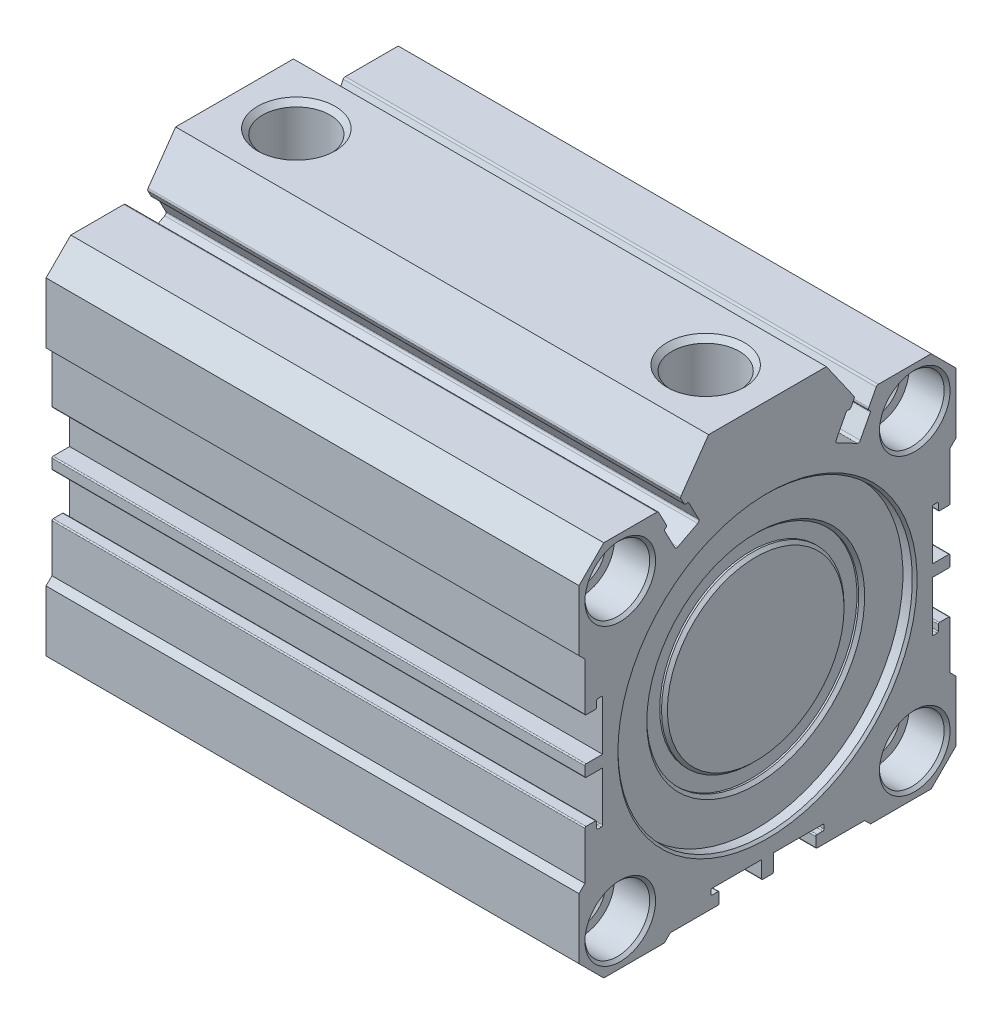
SolidWorks part; units mm, degrees
ref_plane "前视基准面" through (0, 0, 0) normal (0, 0, 1) x (1, 0, 0)
ref_plane "上视基准面" through (0, 0, 0) normal (0, 1, 0) x (1, 0, 0)
ref_plane "右视基准面" through (0, 0, 0) normal (1, 0, 0) x (0, 0, -1)
sketch "草图1" plane through (0, 0, 0) normal (1, 0, 0) x (0, 0, -1)
  line L0 (-32, -17.5) -> (-32, -27.8)
  line L1 (-32, -27.8) -> (-27.8, -32)
  line L2 (-27.8, -32) -> (-17.5, -32)
  line L3 (-17.5, -32) -> (-16.5, -31)
  line L4 (-16.5, -31) -> (-8.4, -31)
  line L5 (-8.2, -30.8) -> (-8.2, -29.2)
  line L6 (-8.4, -29) -> (-9.4, -29)
  line L7 (-9.6, -28.8) -> (-9.6, -28.2)
  line L8 (-9.4, -28) -> (-1, -28)
  line L9 (-1, -28) -> (-1, -30.8)
  line L10 (-0.8, -31) -> (0.8, -31)
  line L11 (1, -30.8) -> (1, -28)
  line L12 (1, -28) -> (9.4, -28)
  line L13 (9.6, -28.2) -> (9.6, -28.8)
  line L14 (9.4, -29) -> (8.4, -29)
  line L15 (8.2, -29.2) -> (8.2, -30.8)
  line L16 (8.4, -31) -> (16.5, -31)
  line L17 (16.5, -31) -> (17.5, -32)
  line L18 (17.5, -32) -> (27.8, -32)
  line L19 (27.8, -32) -> (32, -27.8)
  line L20 (32, -27.8) -> (32, -17.5)
  line L21 (32, -17.5) -> (31, -16.5)
  line L22 (31, -16.5) -> (31, -8.4)
  line L23 (30.8, -8.2) -> (29.2, -8.2)
  line L24 (29, -8.4) -> (29, -9.4)
  line L25 (28.8, -9.6) -> (28.2, -9.6)
  line L26 (28, -9.4) -> (28, -1)
  line L27 (28, -1) -> (30.8, -1)
  line L28 (31, -0.8) -> (31, 0.8)
  line L29 (30.8, 1) -> (28, 1)
  line L30 (28, 1) -> (28, 9.4)
  line L31 (28.2, 9.6) -> (28.8, 9.6)
  line L32 (29, 9.4) -> (29, 8.4)
  line L33 (29.2, 8.2) -> (30.8, 8.2)
  line L34 (31, 8.4) -> (31, 16.5)
  line L35 (31, 16.5) -> (32, 17.5)
  line L36 (32, 17.5) -> (32, 27.8)
  line L37 (32, 27.8) -> (27.8, 32)
  line L38 (27.8, 32) -> (18.8174, 32)
  line L39 (18.4626, 31.7847) -> (17.2074, 29.3734)
  line L40 (17.4625, 28.5641) -> (15.7541, 25.2822)
  line L41 (15.2146, 25.1121) -> (11.8439, 26.8667)
  line L42 (11.6738, 27.4062) -> (13.3823, 30.6882)
  line L43 (14.1915, 30.9433) -> (14.6977, 31.9156)
  line L44 (14.6705, 32.3298) -> (10, 39)
  line L45 (10, 39) -> (-10, 39)
  line L46 (-10, 39) -> (-14.6705, 32.3298)
  line L47 (-14.6977, 31.9156) -> (-14.1915, 30.9433)
  line L48 (-13.3823, 30.6882) -> (-11.6738, 27.4062)
  line L49 (-11.8439, 26.8667) -> (-15.2146, 25.1121)
  line L50 (-15.7541, 25.2822) -> (-17.4625, 28.5641)
  line L51 (-17.2074, 29.3734) -> (-18.4626, 31.7847)
  line L52 (-18.8174, 32) -> (-27.8, 32)
  line L53 (-27.8, 32) -> (-32, 27.8)
  line L54 (-32, 27.8) -> (-32, 17.5)
  line L55 (-32, 17.5) -> (-31, 16.5)
  line L56 (-31, 16.5) -> (-31, 8.4)
  line L57 (-30.8, 8.2) -> (-29.2, 8.2)
  line L58 (-29, 8.4) -> (-29, 9.4)
  line L59 (-28.8, 9.6) -> (-28.2, 9.6)
  line L60 (-28, 9.4) -> (-28, 1)
  line L61 (-28, 1) -> (-30.8, 1)
  line L62 (-31, 0.8) -> (-31, -0.8)
  line L63 (-30.8, -1) -> (-28, -1)
  line L64 (-28, -1) -> (-28, -9.4)
  line L65 (-28.2, -9.6) -> (-28.8, -9.6)
  line L66 (-29, -9.4) -> (-29, -8.4)
  line L67 (-29.2, -8.2) -> (-30.8, -8.2)
  line L68 (-31, -8.4) -> (-31, -16.5)
  line L69 (-31, -16.5) -> (-32, -17.5)
  arc A0 (-8.4, -31) -> (-8.2, -30.8) centre (-8.4, -30.8) ccw
  arc A1 (-8.2, -29.2) -> (-8.4, -29) centre (-8.4, -29.2) ccw
  arc A2 (-9.4, -29) -> (-9.6, -28.8) centre (-9.4, -28.8) cw
  arc A3 (-9.6, -28.2) -> (-9.4, -28) centre (-9.4, -28.2) cw
  arc A4 (-1, -30.8) -> (-0.8, -31) centre (-0.8, -30.8) ccw
  arc A5 (0.8, -31) -> (1, -30.8) centre (0.8, -30.8) ccw
  arc A6 (9.4, -28) -> (9.6, -28.2) centre (9.4, -28.2) cw
  arc A7 (9.6, -28.8) -> (9.4, -29) centre (9.4, -28.8) cw
  arc A8 (8.4, -29) -> (8.2, -29.2) centre (8.4, -29.2) ccw
  arc A9 (8.2, -30.8) -> (8.4, -31) centre (8.4, -30.8) ccw
  arc A10 (31, -8.4) -> (30.8, -8.2) centre (30.8, -8.4) ccw
  arc A11 (29.2, -8.2) -> (29, -8.4) centre (29.2, -8.4) ccw
  arc A12 (29, -9.4) -> (28.8, -9.6) centre (28.8, -9.4) cw
  arc A13 (28.2, -9.6) -> (28, -9.4) centre (28.2, -9.4) cw
  arc A14 (30.8, -1) -> (31, -0.8) centre (30.8, -0.8) ccw
  arc A15 (31, 0.8) -> (30.8, 1) centre (30.8, 0.8) ccw
  arc A16 (28, 9.4) -> (28.2, 9.6) centre (28.2, 9.4) cw
  arc A17 (28.8, 9.6) -> (29, 9.4) centre (28.8, 9.4) cw
  arc A18 (29, 8.4) -> (29.2, 8.2) centre (29.2, 8.4) ccw
  arc A19 (30.8, 8.2) -> (31, 8.4) centre (30.8, 8.4) ccw
  arc A20 (18.8174, 32) -> (18.4626, 31.7847) centre (18.8174, 31.6) ccw
  arc A21 (17.2074, 29.3734) -> (17.3775, 28.8339) centre (17.5622, 29.1887) ccw
  arc A22 (17.3775, 28.8339) -> (17.4625, 28.5641) centre (17.2851, 28.6565) cw
  arc A23 (15.7541, 25.2822) -> (15.2146, 25.1121) centre (15.3993, 25.4669) cw
  arc A24 (11.8439, 26.8667) -> (11.6738, 27.4062) centre (12.0286, 27.2215) cw
  arc A25 (13.3823, 30.6882) -> (13.652, 30.7732) centre (13.5597, 30.5958) cw
  arc A26 (13.652, 30.7732) -> (14.1915, 30.9433) centre (13.8367, 31.128) ccw
  arc A27 (14.6977, 31.9156) -> (14.6705, 32.3298) centre (14.3429, 32.1003) ccw
  arc A28 (-14.6705, 32.3298) -> (-14.6977, 31.9156) centre (-14.3429, 32.1003) ccw
  arc A29 (-14.1915, 30.9433) -> (-13.652, 30.7732) centre (-13.8367, 31.128) ccw
  arc A30 (-13.652, 30.7732) -> (-13.3823, 30.6882) centre (-13.5597, 30.5958) cw
  arc A31 (-11.6738, 27.4062) -> (-11.8439, 26.8667) centre (-12.0286, 27.2215) cw
  arc A32 (-15.2146, 25.1121) -> (-15.7541, 25.2822) centre (-15.3993, 25.4669) cw
  arc A33 (-17.4625, 28.5641) -> (-17.3775, 28.8339) centre (-17.2851, 28.6565) cw
  arc A34 (-17.3775, 28.8339) -> (-17.2074, 29.3734) centre (-17.5622, 29.1887) ccw
  arc A35 (-18.4626, 31.7847) -> (-18.8174, 32) centre (-18.8174, 31.6) ccw
  arc A36 (-31, 8.4) -> (-30.8, 8.2) centre (-30.8, 8.4) ccw
  arc A37 (-29.2, 8.2) -> (-29, 8.4) centre (-29.2, 8.4) ccw
  arc A38 (-29, 9.4) -> (-28.8, 9.6) centre (-28.8, 9.4) cw
  arc A39 (-28.2, 9.6) -> (-28, 9.4) centre (-28.2, 9.4) cw
  arc A40 (-30.8, 1) -> (-31, 0.8) centre (-30.8, 0.8) ccw
  arc A41 (-31, -0.8) -> (-30.8, -1) centre (-30.8, -0.8) ccw
  arc A42 (-28, -9.4) -> (-28.2, -9.6) centre (-28.2, -9.4) cw
  arc A43 (-28.8, -9.6) -> (-29, -9.4) centre (-28.8, -9.4) cw
  arc A44 (-29, -8.4) -> (-29.2, -8.2) centre (-29.2, -8.4) ccw
  arc A45 (-30.8, -8.2) -> (-31, -8.4) centre (-30.8, -8.4) ccw
extrude "凸台-拉伸1" add sketch "草图1" along normal blind 90.5
ref_plane "基准面1" through (0, 0, 25) normal (0, 0, 1) x (1, 0, 0)
sketch "草图2" plane through (0, 0, 25) normal (0, 0, 1) x (1, 0, 0)
  line L0 (0, -25) -> (0, -19.25)
  line L1 (0, -19.25) -> (0.5, -19.75)
  line L2 (0.5, -19.75) -> (6.5, -19.75)
  line L3 (6.5, -19.75) -> (6.5, -21)
  line L4 (6.5, -21) -> (7.1765, -21.6765)
  line L5 (7.1765, -21.6765) -> (45.25, -21.6765)
  line L6 (45.25, -21.6765) -> (45.25, -25)
  line L7 (45.25, -25) -> (0, -25)
  line L8 (45.25, -25) -> (0, -25) construction
revolve "切除-旋转1" cut sketch "草图2" angle 360 about L8 reverse direction yes
cosmetic thread "装饰螺纹线1" parameters "D1"=15.5, "D2"=8
cosmetic thread "装饰螺纹线2" parameters "D1"=15.5, "D2"=8
sketch "草图3" plane through (0, 0, 0) normal (1, 0, 0) x (0, 0, -1)
  line L0 (-25, -25) -> (25, -25)
  line L1 (-25, -25) -> (-25, 25)
pattern_linear "阵列(线性)1" count 2 spacing 50 along (0, 0, -1) count 2 spacing 50 along (0, 1, 0) of "切除-旋转1"
sketch "草图4" plane through (0, 0, 25) normal (0, 0, 1) x (1, 0, 0)
  line L0 (45.25, -25) -> (45.25, -21.6765)
  line L1 (45.25, -21.6765) -> (83.3235, -21.6765)
  line L2 (83.3235, -21.6765) -> (84, -21)
  line L3 (84, -21) -> (84, -19.5)
  line L4 (84, -19.5) -> (90, -19.5)
  line L5 (90, -19.5) -> (90.5, -19)
  line L6 (90.5, -19) -> (90.5, -25)
  line L7 (90.5, -25) -> (45.25, -25)
  line L8 (90.5, -25) -> (45.25, -25) construction
revolve "切除-旋转2" cut sketch "草图4" angle 360 about L8 reverse direction yes
ref_plane "基准面2" through (90.5, 0, 0) normal (1, 0, 0) x (0, 0, -1)
sketch "草图5" plane through (90.5, 0, 0) normal (1, 0, 0) x (0, 0, -1)
  line L0 (-25, -25) -> (25, -25)
  line L1 (-25, -25) -> (-25, 25)
pattern_linear "阵列(线性)2" count 2 spacing 50 along (0, 0, -1) count 2 spacing 50 along (0, 1, 0) of "切除-旋转2"
sketch "草图6" plane through (0, 0, 0) normal (0, 0, 1) x (1, 0, 0)
  line L0 (0, 0) -> (0, 10)
  line L1 (0, 10) -> (10.5, 10)
  line L2 (10.5, 10) -> (10.5, 25)
  line L3 (10.5, 25) -> (83, 25)
  line L4 (83, 25) -> (83, 0)
  line L5 (83, 0) -> (0, 0)
  line L6 (83, 0) -> (0, 0) construction
revolve "切除-旋转3" cut sketch "草图6" angle 360 about L6 reverse direction yes
sketch "草图7" plane through (0, 0, 0) normal (0, 0, 1) x (1, 0, 0)
  line L0 (0, 0) -> (0, 25.4)
  line L1 (0, 25.4) -> (0.4, 25)
  line L2 (0.4, 25) -> (4, 25)
  line L3 (4, 25) -> (4, 0)
  line L4 (4, 0) -> (0, 0)
  line L5 (4, 0) -> (0, 0) construction
revolve "切除-旋转4" cut sketch "草图7" angle 360 about L5 reverse direction yes
ref_plane "基准面3" through (2, 0, 0) normal (1, 0, 0) x (0, 0, -1)
sketch "草图8" plane through (0, 0, 0) normal (0, 0, 1) x (1, 0, 0)
  line L0 (10.5, 39) -> (17.0785, 39)
  line L1 (17.0785, 39) -> (16.2225, 38.144)
  line L2 (16.2225, 38.144) -> (16.2225, 29)
  line L3 (16.2225, 29) -> (10.5, 29)
  line L4 (10.5, 29) -> (10.5, 39)
  line L5 (10.5, 29) -> (10.5, 39) construction
revolve "切除-旋转5" cut sketch "草图8" angle 360 about L5 reverse direction yes
cosmetic thread "装饰螺纹线3" parameters "D1"=10, "D2"=13.157
sketch "草图9" plane through (0, 0, 0) normal (0, 0, 1) x (1, 0, 0)
  line L0 (80, 39) -> (86.5785, 39)
  line L1 (86.5785, 39) -> (85.7225, 38.144)
  line L2 (85.7225, 38.144) -> (85.7225, 29)
  line L3 (85.7225, 29) -> (80, 29)
  line L4 (80, 29) -> (80, 39)
  line L5 (80, 29) -> (80, 39) construction
revolve "切除-旋转6" cut sketch "草图9" angle 360 about L5 reverse direction yes
cosmetic thread "装饰螺纹线4" parameters "D1"=10, "D2"=13.157
sketch "草图10" plane through (0, 0, 0) normal (0, 0, 1) x (1, 0, 0)
  line L0 (0.5, 17) -> (0.5, 10)
  line L1 (0.5, 10) -> (4, 10)
  line L2 (4, 10) -> (4, 17.5)
  line L3 (4, 17.5) -> (1, 17.5)
  line L4 (4, 0) -> (0.5, 0) construction
  arc A0 (1, 17.5) -> (0.5, 17) centre (1, 17) ccw
revolve "旋转1" add sketch "草图10" angle 360 about L4 reverse direction yes
sketch "草图11" plane through (0, 0, 0) normal (0, 0, 1) x (1, 0, 0)
  line L0 (88.5, 0) -> (88.5, 25)
  line L1 (88.5, 25) -> (90.1, 25)
  line L2 (90.1, 25) -> (90.5, 25.4)
  line L3 (90.5, 25.4) -> (90.5, 0)
  line L4 (90.5, 0) -> (88.5, 0)
  line L5 (90.5, 0) -> (88.5, 0) construction
revolve "切除-旋转7" cut sketch "草图11" angle 360 about L5 reverse direction yes
ref_plane "基准面4" through (90.5, 0, 0) normal (1, 0, 0) x (0, 0, -1)
ref_plane "基准面5" through (0, 29, 0) normal (0, 1, 0) x (1, 0, 0)
sketch "草图12" plane through (0, 0, 0) normal (0, 0, 1) x (1, 0, 0)
  line L0 (87.7, 15.5) -> (88, 15.5)
  line L1 (88, 15.5) -> (88.5, 15)
  line L2 (88.5, 15) -> (88.5, 18.5)
  line L3 (88.5, 18.5) -> (88, 18)
  line L4 (88, 18) -> (87.7, 18)
  line L5 (87.7, 18) -> (87.7, 15.5)
  line L6 (50, 0) -> (-50, 0) construction
revolve "切除-旋转8" cut sketch "草图12" angle 360 about L6 reverse direction yes
ref_plane "基准面6" through (1, 0, 0) normal (1, 0, 0) x (0, 0, -1)
ref_plane "基准面7" through (89.5, 0, 0) normal (1, 0, 0) x (0, 0, -1)
ref_plane "IP_SWITCH1 XY" through (1, 0, 0) normal (-1, 0, 0) x (0, 0, 1)
ref_plane "IP_SWITCH1 XZ" through (0, 25.9894, 0) normal (0, 1, 0) x (1, 0, 0)
ref_plane "IP_SWITCH1 YZ" through (0, 0, -13.5292) normal (0, 0, -1) x (-1, 0, 0)
ref_axis "IP_SWITCH1 X" through (1, 25.9894, 80.9) along (0, 0, -1)
ref_axis "IP_SWITCH1 Y" through (1, 50, -13.5292) along (0, -1, 0)
ref_axis "IP_SWITCH1 Z" through (-80.9, 25.9894, -13.5292) along (1, 0, 0)
sketch3d "IP_SWITCH1"
  point P0 (1, 25.9894, -13.5292)
ref_plane "IP_SWITCH2 XY" through (89.5, 0, 0) normal (1, 0, 0) x (0, 0, -1)
ref_plane "IP_SWITCH2 XZ" through (0, 25.9894, 0) normal (0, -1, 0) x (-1, 0, 0)
ref_plane "IP_SWITCH2 YZ" through (0, 0, 13.5292) normal (0, 0, -1) x (-1, 0, 0)
ref_axis "IP_SWITCH2 X" through (89.5, 25.9894, 80.9) along (0, 0, -1)
ref_axis "IP_SWITCH2 Y" through (89.5, -50, 13.5292) along (0, 1, 0)
ref_axis "IP_SWITCH2 Z" through (80.9, 25.9894, 13.5292) along (-1, 0, 0)
sketch3d "IP_SWITCH2"
  point P0 (89.5, 25.9894, 13.5292)
ref_plane "IP_SWITCH3 XY" through (1, 0, 0) normal (-1, 0, 0) x (0, 0, 1)
ref_plane "IP_SWITCH3 XZ" through (0, 1, 0) normal (0, 1, 0) x (1, 0, 0)
ref_plane "IP_SWITCH3 YZ" through (0, 0, -28) normal (0, 0, -1) x (-1, 0, 0)
ref_axis "IP_SWITCH3 X" through (1, 1, 80.9) along (0, 0, -1)
ref_axis "IP_SWITCH3 Y" through (1, 50, -28) along (0, -1, 0)
ref_axis "IP_SWITCH3 Z" through (-80.9, 1, -28) along (1, 0, 0)
sketch3d "IP_SWITCH3"
  point P0 (1, 1, -28)
ref_plane "IP_SWITCH4 XY" through (89.5, 0, 0) normal (1, 0, 0) x (0, 0, -1)
ref_plane "IP_SWITCH4 XZ" through (0, -1, 0) normal (0, -1, 0) x (-1, 0, 0)
ref_plane "IP_SWITCH4 YZ" through (0, 0, 28) normal (0, 0, -1) x (-1, 0, 0)
ref_axis "IP_SWITCH4 X" through (89.5, -1, 80.9) along (0, 0, -1)
ref_axis "IP_SWITCH4 Y" through (89.5, -50, 28) along (0, 1, 0)
ref_axis "IP_SWITCH4 Z" through (80.9, -1, 28) along (-1, 0, 0)
sketch3d "IP_SWITCH4"
  point P0 (89.5, -1, 28)
ref_plane "for_dummy XY" through (0, 0, 0) normal (-1, 0, 0) x (0, 0, 1)
ref_plane "for_dummy XZ" through (0, 0, 0) normal (0, 1, 0) x (1, 0, 0)
ref_plane "for_dummy YZ" through (0, 0, 0) normal (0, 0, -1) x (-1, 0, 0)
ref_axis "for_dummy X" through (0, 0, 80.9) along (0, 0, -1)
ref_axis "for_dummy Y" through (0, 50, 0) along (0, -1, 0)
ref_axis "for_dummy Z" through (-80.9, 0, 0) along (1, 0, 0)
sketch3d "for_dummy"
  point P0 (0, 0, 0)
ref_plane "for_mouanting XY" through (90.5, 0, 0) normal (1, 0, 0) x (0, 0, -1)
ref_plane "for_mouanting XZ" through (0, 0, 0) normal (0, -1, 0) x (-1, 0, 0)
ref_plane "for_mouanting YZ" through (0, 0, 0) normal (0, 0, -1) x (-1, 0, 0)
ref_axis "for_mouanting X" through (90.5, 0, 80.9) along (0, 0, -1)
ref_axis "for_mouanting Y" through (90.5, -50, 0) along (0, 1, 0)
ref_axis "for_mouanting Z" through (80.9, 0, 0) along (-1, 0, 0)
sketch3d "for_mouanting"
  point P0 (90.5, 0, 0)
ref_plane "for_s XY" through (0, 29, 0) normal (0, 1, 0) x (1, 0, 0)
ref_plane "for_s XZ" through (0, 0, 0) normal (0, 0, 1) x (1, 0, 0)
ref_plane "for_s YZ" through (10.5, 0, 0) normal (1, 0, 0) x (0, 0, -1)
ref_axis "for_s X" through (-80.9, 29, 0) along (1, 0, 0)
ref_axis "for_s Y" through (10.5, 29, 50) along (0, 0, -1)
ref_axis "for_s Z" through (10.5, 50, 0) along (0, -1, 0)
sketch3d "for_s"
  point P0 (10.5, 29, 0)
ref_plane "for_s_2 XY" through (0, 29, 0) normal (0, 1, 0) x (1, 0, 0)
ref_plane "for_s_2 XZ" through (0, 0, 0) normal (0, 0, 1) x (1, 0, 0)
ref_plane "for_s_2 YZ" through (80, 0, 0) normal (1, 0, 0) x (0, 0, -1)
ref_axis "for_s_2 X" through (-80.9, 29, 0) along (1, 0, 0)
ref_axis "for_s_2 Y" through (80, 29, 50) along (0, 0, -1)
ref_axis "for_s_2 Z" through (80, 50, 0) along (0, -1, 0)
sketch3d "for_s_2"
  point P0 (80, 29, 0)
